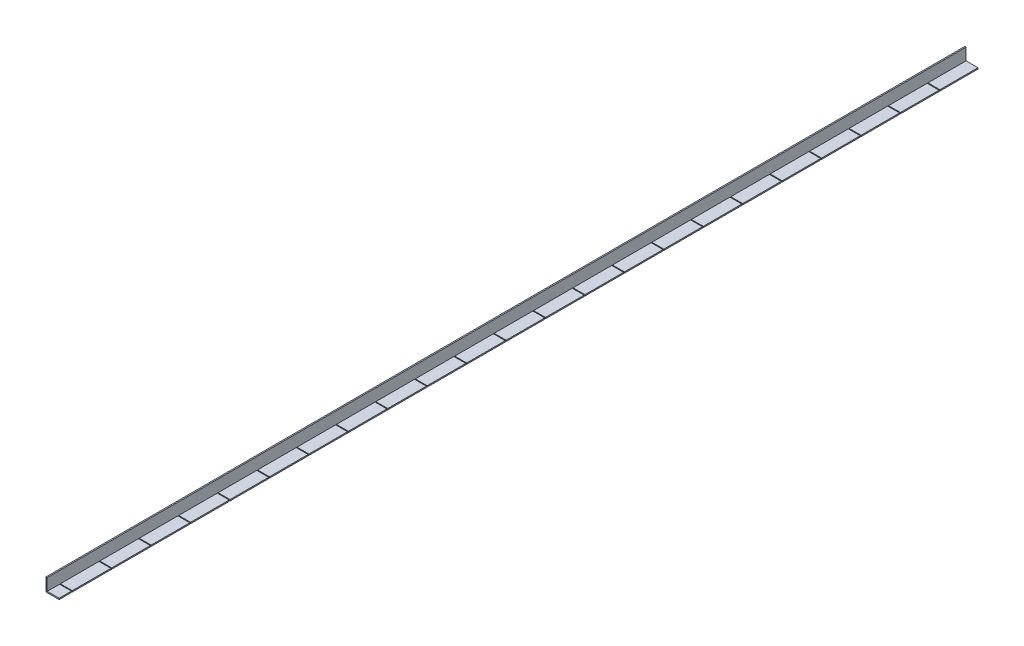
SolidWorks part; units mm, degrees
ref_plane "Front Plane" through (0, 0, 0) normal (0, 0, 1) x (1, 0, 0)
ref_plane "Top Plane" through (0, 0, 0) normal (0, 1, 0) x (1, 0, 0)
ref_plane "Right Plane" through (0, 0, 0) normal (1, 0, 0) x (0, 0, -1)
sketch "Sketch1" plane through (0, 0, 0) normal (0, 0, 1) x (1, 0, 0)
  line L1 (0, 0) -> (50.8, 0)
  line L2 (0, 0) -> (0, 50.8)
  line L3 (0, 50.8) -> (4.7625, 50.8)
  line L4 (50.8, 0) -> (50.8, 4.7625)
  line L7 (50.8, 4.7625) -> (4.7625, 4.7625)
  line L8 (4.7625, 50.8) -> (4.7625, 4.7625)
  dimension "D1" = 50.8
  dimension "D2" = 50.8
  dimension "D3" = 46.0375
  dimension "D4" = 46.0375
extrude "Boss-Extrude1" add sketch "Sketch1" along normal blind 3550.92
sketch "Sketch2" plane through (4.7625, 0, 0) normal (1, 0, 0) x (0, 0, -1)
  line L0 (-3550.92, 4.7625) -> (0, 4.7625) construction
  line L1 (-150.495, 4.7625) -> (-147.32, 4.7625)
  line L2 (-150.495, 4.7625) -> (-150.495, -5.2778)
  line L3 (-150.495, -5.2778) -> (-147.32, -5.2778)
  line L4 (-147.32, 4.7625) -> (-147.32, -5.2778)
  dimension "D1" = 3.175
  dimension "D2" = 147.32
extrude "Cut-Extrude1" cut sketch "Sketch2" along normal blind 80
pattern_linear "LPattern1" count 23 spacing 152.4 along (0, 0, 1) of "Cut-Extrude1"
